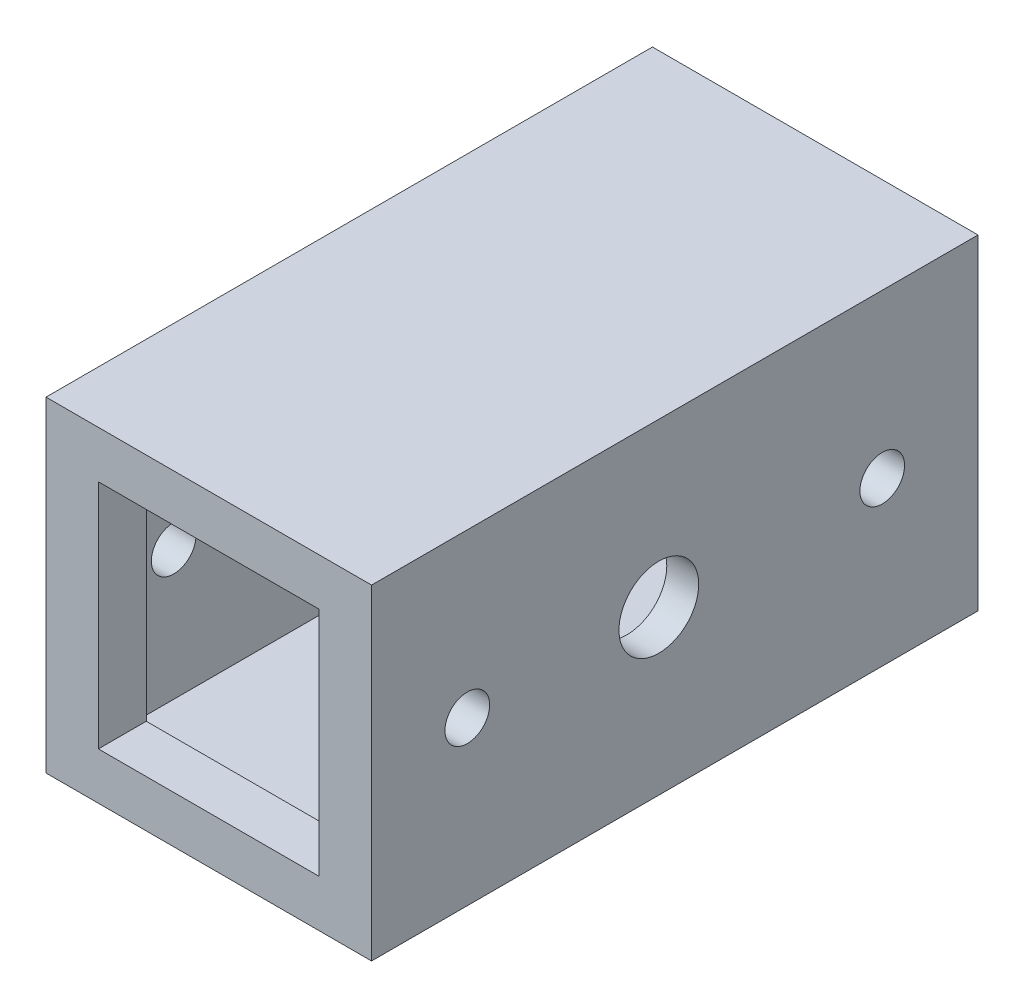
SolidWorks part; units mm, degrees
ref_plane "Front Plane" through (0, 0, 0) normal (0, 0, 1) x (1, 0, 0)
ref_plane "Top Plane" through (0, 0, 0) normal (0, 1, 0) x (1, 0, 0)
ref_plane "Right Plane" through (0, 0, 0) normal (1, 0, 0) x (0, 0, -1)
ref_axis "Axis1" through (0, 0, 0.5) along (0, 0, -1)
sketch "Sketch1" plane through (0, 0, 0) normal (0, 0, 1) x (1, 0, 0)
  line L5 (-10.2, -10.2) -> (10.2, -10.2)
  line L14 (-10.2, -10.2) -> (-10.2, 10.2)
  line L15 (-10.2, 10.2) -> (10.2, 10.2)
  line L16 (10.2, -10.2) -> (10.2, 10.2)
  line L17 (-10.2, -10.2) -> (10.2, 10.2) construction
  line L18 (-10.2, 10.2) -> (10.2, -10.2) construction
  line L19 (-8.2, -8.2) -> (8.2, -8.2)
  line L20 (-8.2, -8.2) -> (-8.2, 8.2)
  line L21 (-8.2, 8.2) -> (8.2, 8.2)
  line L22 (8.2, -8.2) -> (8.2, 8.2)
  line L23 (-8.2, -8.2) -> (8.2, 8.2) construction
  line L24 (-8.2, 8.2) -> (8.2, -8.2) construction
  point P0 (0, 0)
  point P6 (0, 0)
  dimension "D1" = 16.4
  dimension "D2" = 2
extrude "Boss-Extrude1" add sketch "Sketch1" against normal blind 35
sketch "Sketch2" plane through (0, 0, 0) normal (0, 0, 1) x (1, 0, 0)
  line L1 (10.2, 10.2) -> (-10.2, 10.2)
  line L2 (10.2, 10.2) -> (10.2, -10.2)
  line L3 (10.2, -10.2) -> (-10.2, -10.2)
  line L4 (-10.2, 10.2) -> (-10.2, -10.2)
  line L9 (6.9174, -7.2486) -> (-6.9174, -7.2486)
  line L10 (6.9174, -7.2486) -> (6.9174, 7.2486)
  line L11 (6.9174, 7.2486) -> (-6.9174, 7.2486)
  line L12 (-6.9174, -7.2486) -> (-6.9174, 7.2486)
  line L13 (6.9174, -7.2486) -> (-6.9174, 7.2486) construction
  line L14 (6.9174, 7.2486) -> (-6.9174, -7.2486) construction
  point P4 (0, 0)
  point P5 (0, 0)
extrude "Boss-Extrude2" add sketch "Sketch2" along normal blind 3
sketch "Sketch3" plane through (10.2, 0, 0) normal (1, 0, 0) x (0, 0, -1)
  circle A0 centre (29, 0) radius 1.6 construction
  circle A2 centre (15, 0) radius 5.5 construction
  circle A15 centre (3, 0) radius 1.6 construction
  circle A16 centre (29, 0) radius 1.6 construction
  circle A17 centre (15, 0) radius 5.5 construction
  circle A18 centre (3, 0) radius 1.6 construction
  circle A19 centre (3, 0) radius 1.4
  circle A20 centre (29, 0) radius 1.4
  circle A21 centre (15, 0) radius 2.5
  dimension "D1" = 2.8
  dimension "D2" = 5
extrude "Cut-Extrude1" cut sketch "Sketch3" against normal through all
fillet "Fillet1" radius 1 4 edges at (-8.2, 0, -35) (0, -8.2, -35) (8.2, 0, -35) (0, 8.2, -35)
